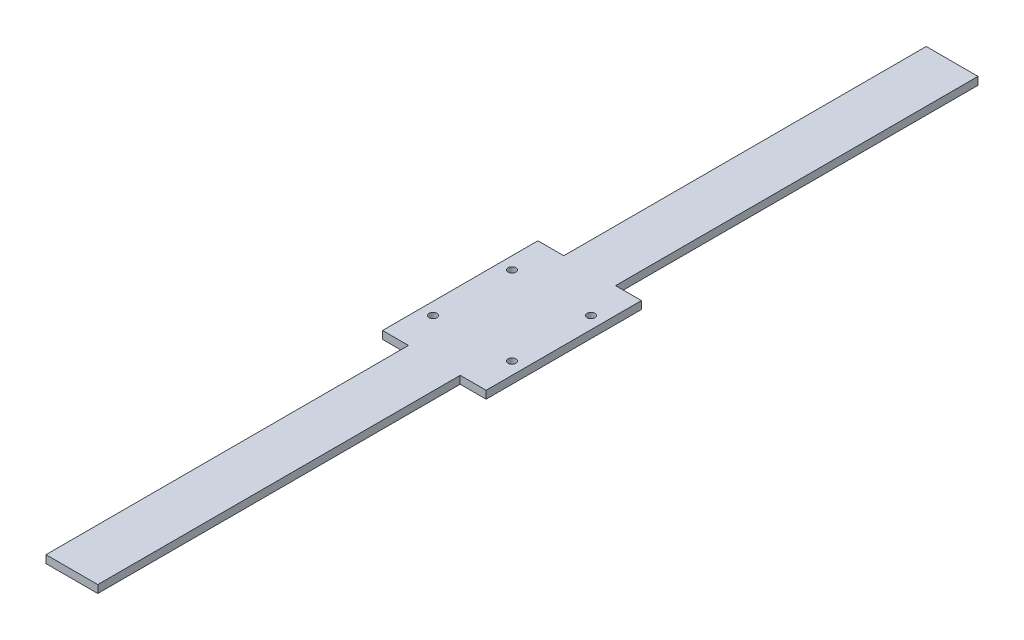
SolidWorks part; units mm, degrees
ref_plane "Front Plane" through (0, 0, 0) normal (0, 0, 1) x (1, 0, 0)
ref_plane "Top Plane" through (0, 0, 0) normal (0, 1, 0) x (1, 0, 0)
ref_plane "Right Plane" through (0, 0, 0) normal (1, 0, 0) x (0, 0, -1)
sketch "Sketch1" plane through (0, 0, 0) normal (0, 1, 0) x (1, 0, 0)
  line L0 (-10, 170) -> (-10, 30)
  line L1 (-15.25, 15.25) -> (15.25, 15.25) construction
  line L2 (-15.25, 15.25) -> (-15.25, -15.25) construction
  line L3 (-15.25, -15.25) -> (15.25, -15.25) construction
  line L4 (15.25, 15.25) -> (15.25, -15.25) construction
  line L5 (-15.25, 15.25) -> (15.25, -15.25) construction
  line L6 (-15.25, -15.25) -> (15.25, 15.25) construction
  line L7 (-20, 170) -> (20, 170) construction
  line L8 (-20, 170) -> (-20, -170) construction
  line L9 (-20, -170) -> (20, -170) construction
  line L10 (20, 170) -> (20, -170) construction
  line L11 (-10, 30) -> (-20, 30)
  line L12 (0, 170) -> (0, -170) construction
  line L13 (-20, 0) -> (20, 0) construction
  line L14 (10, 30) -> (20, 30)
  line L15 (10, 170) -> (10, 30)
  line L16 (10, -30) -> (20, -30)
  line L17 (10, -170) -> (10, -30)
  line L18 (-10, -30) -> (-20, -30)
  line L19 (-10, -170) -> (-10, -30)
  line L20 (-10, -170) -> (10, -170)
  line L21 (20, 30) -> (20, -30)
  line L22 (-20, 30) -> (-20, -30)
  line L23 (-10, 170) -> (10, 170)
  circle A0 centre (-15.25, 15.25) radius 1.5
  circle A1 centre (15.25, 15.25) radius 1.5
  circle A2 centre (15.25, -15.25) radius 1.5
  circle A3 centre (-15.25, -15.25) radius 1.5
  point P0 (0, 0)
  point P14 (0, 170)
  point P15 (-20, 0)
  dimension "D2" = 3
  dimension "D1" = 30.5
  dimension "D3" = 340
  dimension "D4" = 40
  dimension "D5" = 10
  dimension "D6" = 60
extrude "Boss-Extrude1" add sketch "Sketch1" along normal mid plane 3
